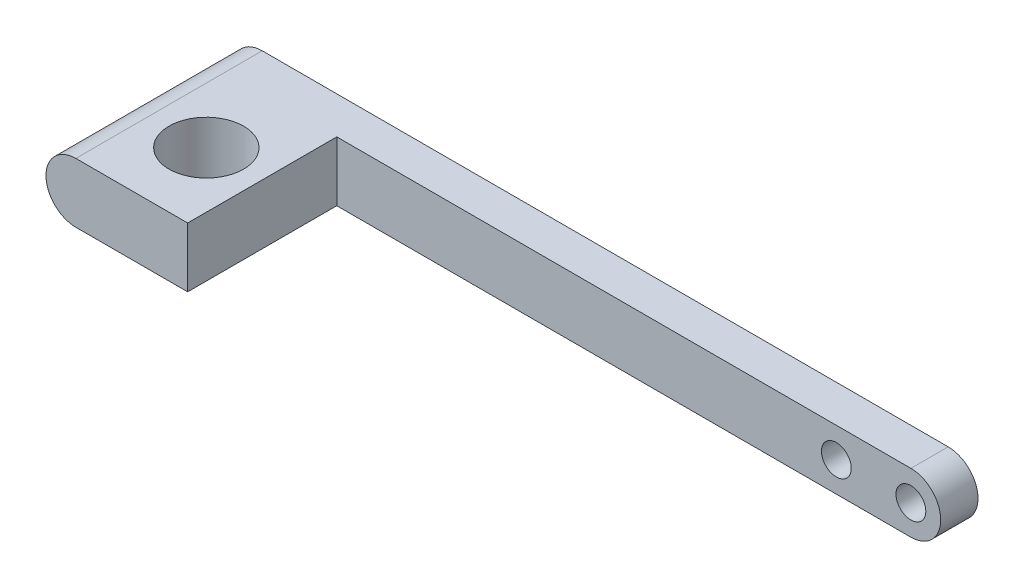
SolidWorks part; units mm, degrees
ref_plane "前视基准面" through (0, 0, 0) normal (0, 0, 1) x (1, 0, 0)
ref_plane "上视基准面" through (0, 0, 0) normal (0, 1, 0) x (1, 0, 0)
ref_plane "右视基准面" through (0, 0, 0) normal (1, 0, 0) x (0, 0, -1)
other "Configuration Table"
sketch "草图1" plane through (0, 0, 0) normal (0, 1, 0) x (1, 0, 0)
  line L22 (-50, -2.5) -> (50, -2.5)
  line L23 (-50, -2.5) -> (-50, 2.5)
  line L28 (-50, 2.5) -> (50, 2.5)
  line L29 (50, -2.5) -> (50, 2.5)
  line L37 (-50, -2.5) -> (50, 2.5) construction
  line L38 (-50, 2.5) -> (50, -2.5) construction
  point P0 (0, 0)
  dimension "D1" = 100
  dimension "D2" = 5
extrude "凸台-拉伸1" add sketch "草图1" along normal blind 8
sketch "草图2" plane through (0, 0, 2.5) normal (0, 0, 1) x (1, 0, 0)
  line L0 (50, 8) -> (50, 0) construction
  circle A0 centre (46, 4) radius 1.1
  circle A1 centre (36, 4) radius 1.1
  circle A2 centre (36, 4) radius 2
  circle A3 centre (46, 4) radius 2
  point P6 (0, 0)
  point P9 (50, 4)
  dimension "D2" = 2.2
  dimension "D3" = 4
  dimension "D1" = 10
  dimension "D4" = 4
extrude "切除-拉伸1" cut sketch "草图2" against normal through all contours A1 | A0
extrude "切除-拉伸2" cut sketch "草图2<3>" against normal offset from surface (3 mm away) 2 contours A2 | A3 up to face at (37.1, 4, -2.5)
sketch "草图2<3>" plane through (0, 0, 2.5) normal (0, 0, 1) x (1, 0, 0) same geometry as "草图2"
sketch "草图3" plane through (0, 0, 2.5) normal (0, 0, 1) x (1, 0, 0)
  line L0 (46, 6.5) -> (46, 1.5) construction
  line L1 (50, 8) -> (50, 0) construction
  line L2 (46, 0) -> (46, 8)
  line L3 (-50, 8) -> (-50, 0) construction
  line L4 (46, 0) -> (50, 0)
  line L5 (46, 0) -> (46, 8)
  line L6 (46, 8) -> (50, 8)
  line L7 (50, 0) -> (50, 8)
  line L8 (-50, 8) -> (50, 8) construction
  line L9 (-50, 0) -> (50, 0) construction
  line L11 (-50, 8) -> (-46, 8)
  line L12 (-50, 8) -> (-50, 0)
  line L13 (-50, 0) -> (-46, 0)
  line L14 (-46, 8) -> (-46, 0)
  circle A0 centre (46, 4) radius 4
  circle A1 centre (-46, 4) radius 4
  line M4 (-50, 0) -> (50, 0)
  line M5 (50, 0) -> (50, 8)
  line M6 (50, 8) -> (-50, 8)
  line M7 (-50, 8) -> (-50, 0)
extrude "切除-拉伸3" cut sketch "草图3" against normal through all contours A0 M4 M5 | A0 L7 M6 region at (49.1065, 0.8935, 2.5) region at (49.1065, 7.1065, 2.5)
extrude "切除-拉伸4" cut sketch "草图3<3>" against normal through all contours A1 M6 M7 | A1 L12 M4 region at (-49.1065, 0.8935, 2.5) region at (-49.1065, 7.1065, 2.5)
sketch "草图3<3>" plane through (0, 0, 2.5) normal (0, 0, 1) x (1, 0, 0) same geometry as "草图3"
sketch "草图4" plane through (0, 0, 2.5) normal (0, 0, 1) x (1, 0, 0)
  line L1 (-46, 0) -> (-31, 0)
  line L2 (-46, 0) -> (46, 0)
  line L3 (46, 8) -> (-46, 8)
  line L4 (-46, 0) -> (46, 0)
  line L5 (46, 8) -> (-46, 8)
  line L6 (-46, 0) -> (-46, 8)
  line L7 (-46, 8) -> (-31, 8)
  line L8 (-31, 0) -> (-31, 8)
  arc A2 (-46, 8) -> (-46, 0) centre (-46, 4) ccw
  arc A3 (46, 0) -> (46, 8) centre (46, 4) ccw
  arc A4 (-46, 8) -> (-46, 0) centre (-46, 4) ccw
  arc A5 (46, 0) -> (46, 8) centre (46, 4) ccw
  arc M11 (-46, 8) -> (-46, 0) centre (-46, 4) ccw
  line M12 (-46, 0) -> (46, 0)
  dimension "D2" = 15
  dimension "D1" = 0
extrude "凸台-拉伸2" add sketch "草图4" along normal blind 20 contours L6 M11 | L8 L5 L6 M12 region at (-38.5, 4, 2.5) region at (-47.6977, 4, 2.5)
sketch "草图5" plane through (0, 0, 0) normal (0, -1, 0) x (1, 0, 0)
  line L0 (-46, 12.5) -> (-31, 12.5)
  line L1 (-46, -2.5) -> (-46, 22.5) construction
  line L2 (-31, 22.5) -> (-31, 2.5) construction
  circle A0 centre (-38.5, 12.5) radius 5
  point P8 (0, 0)
  point P9 (-31, 12.5)
  dimension "D1" = 10
extrude "切除-拉伸5" cut sketch "草图5" against normal through all contours L0 A0 | L0 A0 region at (-38.5, 0, 14.6221) region at (-38.5, 0, 10.3779)
